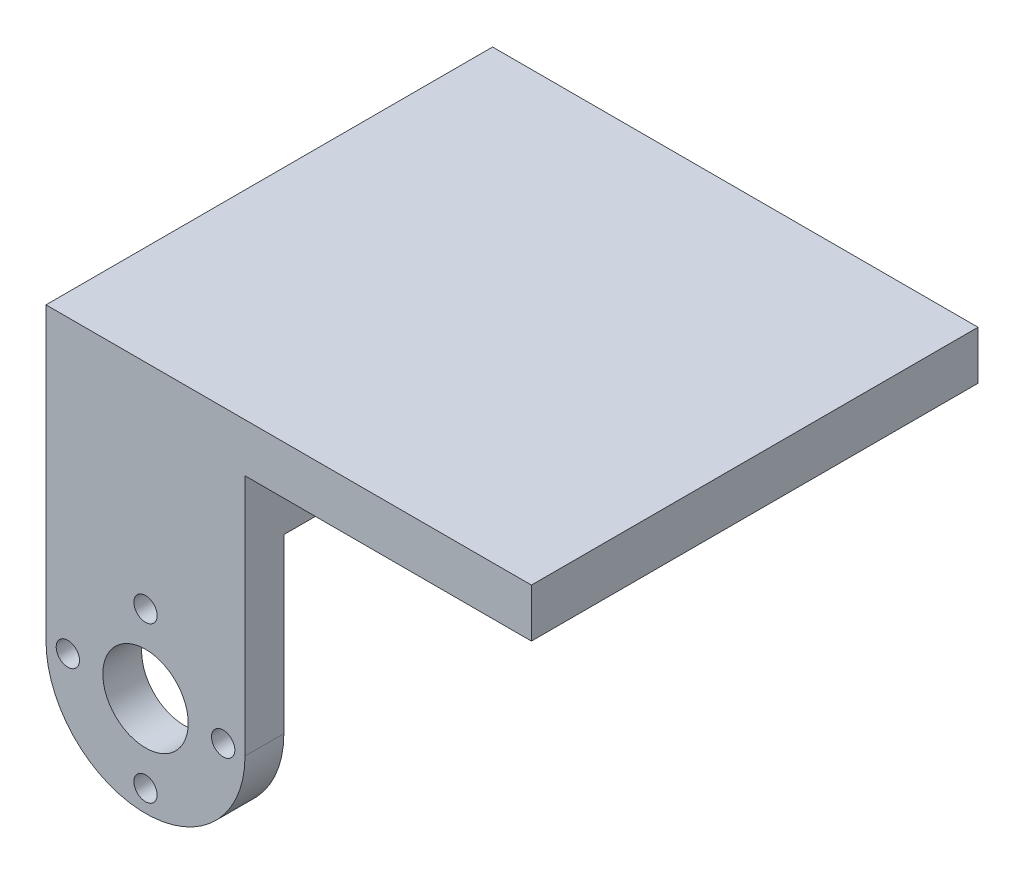
SolidWorks part; units mm, degrees
ref_plane "Front Plane" through (0, 0, 0) normal (0, 0, 1) x (1, 0, 0)
ref_plane "Top Plane" through (0, 0, 0) normal (0, 1, 0) x (1, 0, 0)
ref_plane "Right Plane" through (0, 0, 0) normal (1, 0, 0) x (0, 0, -1)
sketch "Sketch1" plane through (0, 0, 0) normal (0, 0, 1) x (1, 0, 0)
  line L2 (10.25, 0) -> (-10.25, 0)
  line L3 (10.25, 0) -> (10.25, 25)
  line L6 (10.25, 25) -> (-10.25, 25)
  line L9 (-10.25, 0) -> (-10.25, 25)
  line L10 (-10.25, 25) -> (39.75, 25)
  line L11 (-10.25, 25) -> (-10.25, 30)
  line L12 (-10.25, 30) -> (39.75, 30)
  line L13 (39.75, 25) -> (39.75, 30)
  circle A0 centre (0, 0) radius 10.25
  circle A5 centre (0, 0) radius 4.4
  circle A6 centre (0, 0) radius 8
  circle A7 centre (0, 8) radius 1.2
  circle A8 centre (8, 0) radius 1.2
  circle A9 centre (0, -8) radius 1.2
  circle A10 centre (-8, 0) radius 1.2
  point P36 (0, 0)
  dimension "D1" = 25
  dimension "D4" = 5
  dimension "D7" = 8.8
  dimension "D8" = 2.4
  dimension "D3" = 50
  dimension "D9" = 4
extrude "Boss-Extrude1" add sketch "Sketch1" against normal blind 46 contours A0 L3 L6 L9 | A10 A6 A7 A8 L2 A0 | A10 L2 A5 A8 A6 A7 | A10 L2 A0 A8 A6 A9 | A10 A6 A9 A8 L2 A5 | L11 L12 L13 L10 region at (0, -10.0208, 0) region at (0, 16.3708, 0) region at (9.725, 0.2292, 0) region at (6.9906, 0.9364, 0) region at (5.5318, -5.5318, 0)
sketch "Sketch2" plane through (-10.25, 0, 0) normal (-1, 0, 0) x (0, 0, 1)
  line L0 (-46, -10.25) -> (0, -10.25) construction
  line L1 (-4, -10.25) -> (-42, -10.25)
  line L2 (-4, -10.25) -> (-4, 17.75)
  line L3 (-4, 17.75) -> (-42, 17.75)
  line L4 (-42, -10.25) -> (-42, 17.75)
  line L5 (-46, 0) -> (-46, 30) construction
  line L6 (0, -10.25) -> (0, 0) construction
  dimension "D1" = 4
  dimension "D2" = 4
  dimension "D3" = 28
extrude "Cut-Extrude1" cut sketch "Sketch2" against normal blind 46
